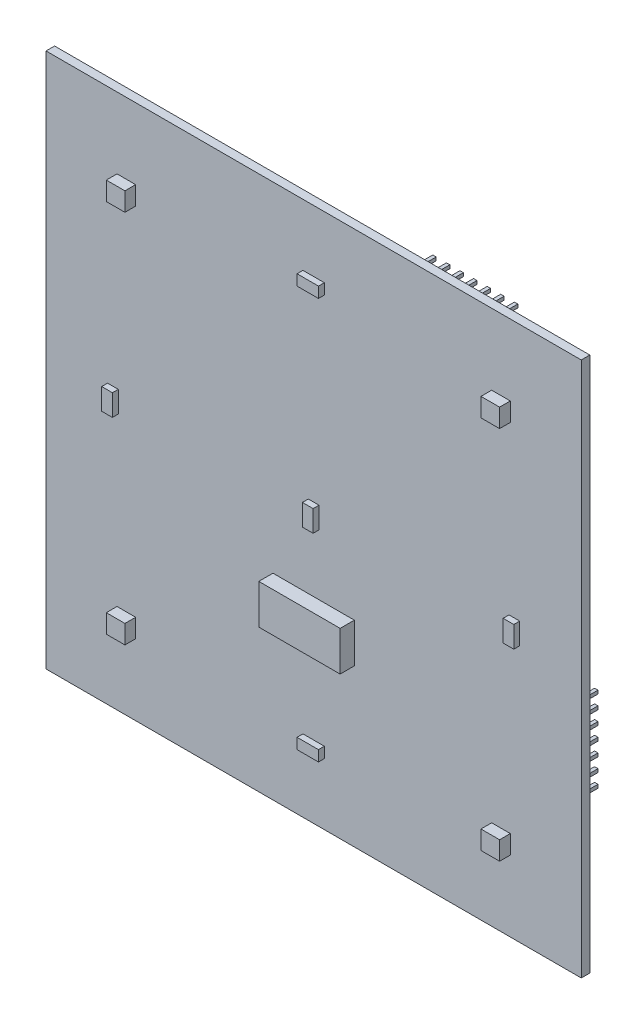
SolidWorks part; units mm, degrees
ref_plane "正面" through (0, 0, 0) normal (0, 0, 1) x (1, 0, 0)
ref_plane "平面" through (0, 0, 0) normal (0, 1, 0) x (1, 0, 0)
ref_plane "右側面" through (0, 0, 0) normal (1, 0, 0) x (0, 0, -1)
sketch "ｽｹｯﾁ1" plane through (0, 0, 0) normal (0, 0, 1) x (1, 0, 0)
  line L0 (-50, 0) -> (50, 0) construction
  line L1 (-50, 50) -> (50, 50)
  line L2 (-50, 50) -> (-50, -50)
  line L3 (-50, -50) -> (50, -50)
  line L4 (50, 50) -> (50, -50)
  line L5 (0, -50) -> (0, 50) construction
  point P8 (0, 0)
  dimension "D1" = 100
  dimension "D2" = 100
  dimension "D3" = 0
  dimension "D4" = 0
extrude "ﾎﾞｽ - 押し出し1" add sketch "ｽｹｯﾁ1" along normal blind 1.6
sketch "ｽｹｯﾁ4" plane through (0, 0, 0) normal (0, 0, -1) x (-1, 0, 0)
  line L0 (-50, -50) -> (-50, 50) construction
  line L1 (11.11, -41.35) -> (28.89, -41.35)
  line L2 (11.11, -41.35) -> (11.11, -43.85)
  line L3 (11.11, -43.85) -> (28.89, -43.85)
  line L4 (28.89, -41.35) -> (28.89, -43.85)
  line L5 (50, -50) -> (-50, -50) construction
  line L6 (50, 50) -> (50, -50) construction
  line L8 (-43.85, -11.11) -> (-41.35, -11.11)
  line L9 (-43.85, -11.11) -> (-43.85, -28.89)
  line L10 (-43.85, -28.89) -> (-41.35, -28.89)
  line L11 (-41.35, -11.11) -> (-41.35, -28.89)
  line L12 (-28.89, 43.85) -> (-11.11, 43.85)
  line L13 (-28.89, 43.85) -> (-28.89, 41.35)
  line L14 (-28.89, 41.35) -> (-11.11, 41.35)
  line L15 (-11.11, 43.85) -> (-11.11, 41.35)
  line L16 (-50, 50) -> (50, 50) construction
  line L18 (41.35, 28.89) -> (43.85, 28.89)
  line L19 (41.35, 28.89) -> (41.35, 11.11)
  line L20 (41.35, 11.11) -> (43.85, 11.11)
  line L21 (43.85, 28.89) -> (43.85, 11.11)
  point P4 (28.89, -42.6)
  point P7 (20, -43.85)
  point P14 (-43.85, -20)
  point P15 (-42.6, -28.89)
  point P22 (-28.89, 42.6)
  point P25 (43.85, 20)
  point P26 (-20, 43.85)
  point P31 (42.6, 28.89)
  dimension "D1" = 7.4
  dimension "D2" = 30
  dimension "D3" = 2.5
  dimension "D4" = 17.78
  dimension "D5" = 2.5
  dimension "D6" = 17.78
  dimension "D7" = 30
  dimension "D8" = 7.4
  dimension "D9" = 2.5
  dimension "D10" = 7.4
  dimension "D11" = 30
  dimension "D12" = 17.78
  dimension "D13" = 17.78
  dimension "D14" = 2.5
  dimension "D15" = 30
  dimension "D16" = 7.4
extrude "ﾎﾞｽ - 押し出し2" add sketch "ｽｹｯﾁ4" along normal blind 2.5
sketch "ｽｹｯﾁ5" plane through (0, 0, -2.5) normal (0, 0, -1) x (-1, 0, 0)
  line L1 (-20.32, 42.92) -> (-19.68, 42.92)
  line L2 (-20.32, 42.92) -> (-20.32, 42.28)
  line L3 (-20.32, 42.28) -> (-19.68, 42.28)
  line L4 (-19.68, 42.92) -> (-19.68, 42.28)
  line L5 (43.85, 28.89) -> (41.35, 28.89) construction
  line L6 (-11.11, 43.85) -> (-28.89, 43.85) construction
  line L7 (-28.89, 43.85) -> (-28.89, 41.35) construction
  line L8 (-43.85, -28.89) -> (-41.35, -28.89) construction
  line L9 (-17.78, 42.92) -> (-17.14, 42.92)
  line L10 (-17.78, 42.92) -> (-17.78, 42.28)
  line L11 (-17.78, 42.28) -> (-17.14, 42.28)
  line L12 (-17.14, 42.92) -> (-17.14, 42.28)
  line L13 (-15.24, 42.92) -> (-14.6, 42.92)
  line L14 (-15.24, 42.92) -> (-15.24, 42.28)
  line L15 (-15.24, 42.28) -> (-14.6, 42.28)
  line L16 (-14.6, 42.92) -> (-14.6, 42.28)
  line L17 (-12.7, 42.92) -> (-12.06, 42.92)
  line L18 (-12.7, 42.92) -> (-12.7, 42.28)
  line L19 (-12.7, 42.28) -> (-12.06, 42.28)
  line L20 (-12.06, 42.92) -> (-12.06, 42.28)
  line L21 (-22.86, 42.92) -> (-22.22, 42.92)
  line L22 (-22.86, 42.92) -> (-22.86, 42.28)
  line L23 (-22.86, 42.28) -> (-22.22, 42.28)
  line L24 (-22.22, 42.92) -> (-22.22, 42.28)
  line L25 (-25.4, 42.92) -> (-24.76, 42.92)
  line L26 (-25.4, 42.92) -> (-25.4, 42.28)
  line L27 (-25.4, 42.28) -> (-24.76, 42.28)
  line L28 (-24.76, 42.92) -> (-24.76, 42.28)
  line L29 (-27.94, 42.92) -> (-27.3, 42.92)
  line L30 (-27.94, 42.92) -> (-27.94, 42.28)
  line L31 (-27.94, 42.28) -> (-27.3, 42.28)
  line L32 (-27.3, 42.92) -> (-27.3, 42.28)
  line L33 (-42.92, -19.68) -> (-42.28, -19.68)
  line L34 (-42.92, -19.68) -> (-42.92, -20.32)
  line L35 (-42.92, -20.32) -> (-42.28, -20.32)
  line L36 (-42.28, -19.68) -> (-42.28, -20.32)
  line L37 (-43.85, -11.11) -> (-43.85, -28.89) construction
  line L38 (43.85, 11.11) -> (43.85, 28.89) construction
  line L39 (-42.92, -22.22) -> (-42.28, -22.22)
  line L40 (-42.92, -22.22) -> (-42.92, -22.86)
  line L41 (-42.92, -22.86) -> (-42.28, -22.86)
  line L42 (-42.28, -22.22) -> (-42.28, -22.86)
  line L44 (42.28, 19.68) -> (42.92, 19.68)
  line L45 (-42.92, -24.76) -> (-42.28, -24.76)
  line L46 (-42.92, -24.76) -> (-42.92, -25.4)
  line L47 (-42.92, -25.4) -> (-42.28, -25.4)
  line L48 (-42.28, -24.76) -> (-42.28, -25.4)
  line L49 (-42.92, -27.3) -> (-42.28, -27.3)
  line L50 (-42.92, -27.3) -> (-42.92, -27.94)
  line L51 (-42.92, -27.94) -> (-42.28, -27.94)
  line L52 (-42.28, -27.3) -> (-42.28, -27.94)
  line L53 (-42.92, -17.14) -> (-42.28, -17.14)
  line L54 (-42.92, -17.14) -> (-42.92, -17.78)
  line L55 (-42.92, -17.78) -> (-42.28, -17.78)
  line L56 (-42.28, -17.14) -> (-42.28, -17.78)
  line L57 (-42.92, -14.6) -> (-42.28, -14.6)
  line L58 (-42.92, -14.6) -> (-42.92, -15.24)
  line L59 (-42.92, -15.24) -> (-42.28, -15.24)
  line L60 (-42.28, -14.6) -> (-42.28, -15.24)
  line L61 (-42.92, -12.06) -> (-42.28, -12.06)
  line L62 (-42.92, -12.06) -> (-42.92, -12.7)
  line L63 (-42.92, -12.7) -> (-42.28, -12.7)
  line L64 (-42.28, -12.06) -> (-42.28, -12.7)
  line L69 (42.28, 19.68) -> (42.28, 20.32)
  line L70 (11.11, -43.85) -> (28.89, -43.85) construction
  line L71 (42.28, 17.78) -> (42.92, 17.78)
  line L72 (42.28, 20.32) -> (42.92, 20.32)
  line L73 (42.92, 19.68) -> (42.92, 20.32)
  line L75 (42.28, 17.78) -> (42.28, 17.14)
  line L76 (42.28, 17.14) -> (42.92, 17.14)
  line L77 (42.92, 17.78) -> (42.92, 17.14)
  line L78 (42.28, 15.24) -> (42.92, 15.24)
  line L79 (42.28, 15.24) -> (42.28, 14.6)
  line L80 (42.28, 14.6) -> (42.92, 14.6)
  line L81 (42.92, 15.24) -> (42.92, 14.6)
  line L82 (42.28, 12.7) -> (42.92, 12.7)
  line L83 (42.28, 12.7) -> (42.28, 12.06)
  line L84 (42.28, 12.06) -> (42.92, 12.06)
  line L85 (42.92, 12.7) -> (42.92, 12.06)
  line L86 (42.28, 22.86) -> (42.92, 22.86)
  line L87 (42.28, 22.86) -> (42.28, 22.22)
  line L88 (42.28, 22.22) -> (42.92, 22.22)
  line L89 (42.92, 22.86) -> (42.92, 22.22)
  line L90 (42.28, 25.4) -> (42.92, 25.4)
  line L91 (42.28, 25.4) -> (42.28, 24.76)
  line L92 (42.28, 24.76) -> (42.92, 24.76)
  line L93 (42.92, 25.4) -> (42.92, 24.76)
  line L94 (42.28, 27.94) -> (42.92, 27.94)
  line L95 (42.28, 27.94) -> (42.28, 27.3)
  line L96 (42.28, 27.3) -> (42.92, 27.3)
  line L97 (42.92, 27.94) -> (42.92, 27.3)
  line L98 (19.68, -42.28) -> (20.32, -42.28)
  line L99 (19.68, -42.28) -> (19.68, -42.92)
  line L100 (19.68, -42.92) -> (20.32, -42.92)
  line L101 (20.32, -42.28) -> (20.32, -42.92)
  line L102 (11.11, -41.35) -> (11.11, -43.85) construction
  line L104 (17.14, -42.28) -> (17.78, -42.28)
  line L105 (17.14, -42.28) -> (17.14, -42.92)
  line L106 (17.14, -42.92) -> (17.78, -42.92)
  line L107 (17.78, -42.28) -> (17.78, -42.92)
  line L108 (14.6, -42.28) -> (15.24, -42.28)
  line L109 (14.6, -42.28) -> (14.6, -42.92)
  line L110 (14.6, -42.92) -> (15.24, -42.92)
  line L111 (15.24, -42.28) -> (15.24, -42.92)
  line L112 (12.06, -42.28) -> (12.7, -42.28)
  line L113 (12.06, -42.28) -> (12.06, -42.92)
  line L114 (12.06, -42.92) -> (12.7, -42.92)
  line L115 (12.7, -42.28) -> (12.7, -42.92)
  line L116 (22.22, -42.28) -> (22.86, -42.28)
  line L117 (22.22, -42.28) -> (22.22, -42.92)
  line L118 (22.22, -42.92) -> (22.86, -42.92)
  line L119 (22.86, -42.28) -> (22.86, -42.92)
  line L120 (24.76, -42.28) -> (25.4, -42.28)
  line L121 (24.76, -42.28) -> (24.76, -42.92)
  line L122 (24.76, -42.92) -> (25.4, -42.92)
  line L123 (25.4, -42.28) -> (25.4, -42.92)
  line L124 (27.3, -42.28) -> (27.94, -42.28)
  line L125 (27.3, -42.28) -> (27.3, -42.92)
  line L126 (27.3, -42.92) -> (27.94, -42.92)
  line L127 (27.94, -42.28) -> (27.94, -42.92)
  point P4 (-20, 42.92)
  point P7 (-20, 43.85)
  point P8 (-20.32, 42.6)
  point P11 (-28.89, 42.6)
  point P16 (-20, 42.28)
  point P17 (-17.46, 42.28)
  point P22 (-14.92, 42.28)
  point P27 (-12.38, 42.28)
  point P40 (-22.54, 42.28)
  point P41 (-25.08, 42.28)
  point P42 (-27.62, 42.28)
  point P47 (-42.6, -20.32)
  point P50 (-42.6, -28.89)
  point P53 (-42.92, -20)
  point P54 (-43.85, -20)
  point P59 (-42.28, -22.54)
  point P60 (-42.28, -20)
  point P61 (-42.28, -25.08)
  point P70 (-42.28, -27.62)
  point P83 (-42.28, -17.46)
  point P84 (-42.28, -14.92)
  point P85 (-42.28, -12.38)
  point P90 (42.6, 19.68)
  point P93 (42.6, 28.89)
  point P94 (42.92, 20)
  point P97 (43.85, 20)
  point P110 (42.28, 12.38)
  point P111 (42.28, 14.92)
  point P112 (42.28, 17.46)
  point P113 (42.28, 20)
  point P126 (42.28, 22.54)
  point P127 (42.28, 25.08)
  point P128 (42.28, 27.62)
  point P133 (20, -42.92)
  point P136 (20, -43.85)
  point P139 (11.11, -42.6)
  point P140 (19.68, -42.6)
  point P165 (17.46, -42.28)
  point P166 (20, -42.28)
  point P167 (14.92, -42.28)
  point P168 (12.38, -42.28)
  point P169 (22.54, -42.28)
  point P170 (25.08, -42.28)
  point P171 (27.62, -42.28)
  point P173 (12.06, -42.6)
  point P174 (14.6, -42.6)
  point P175 (17.14, -42.6)
  point P176 (22.22, -42.6)
  point P177 (24.76, -42.6)
  point P178 (27.3, -42.6)
  point P179 (-42.6, -27.3)
  point P180 (-42.6, -24.76)
  point P181 (-42.6, -22.22)
  point P182 (-42.6, -19.68)
  point P183 (-42.6, -17.14)
  point P184 (-42.6, -14.6)
  point P185 (-42.6, -12.06)
  point P186 (-27.94, 42.6)
  point P187 (-25.4, 42.6)
  point P188 (-22.86, 42.6)
  point P189 (-17.78, 42.6)
  point P190 (-15.24, 42.6)
  point P191 (-12.7, 42.6)
  point P192 (42.6, 15.24)
  point P193 (42.6, 17.78)
  point P194 (42.6, 20.32)
  point P195 (42.6, 22.86)
  point P196 (42.6, 25.4)
  point P197 (42.6, 27.94)
  point P198 (42.6, 12.7)
  dimension "D1" = 0.64
  dimension "D2" = 0.64
  dimension "D3" = 0.64
  dimension "D4" = 0.64
  dimension "D5" = 2.54
  dimension "D6" = 0.64
  dimension "D7" = 2.54
  dimension "D8" = 0.64
  dimension "D9" = 0.64
  dimension "D10" = 0.64
  dimension "D11" = 2.54
  dimension "D12" = 0.64
  dimension "D13" = 0.64
  dimension "D14" = 0.64
  dimension "D15" = 2.54
  dimension "D16" = 0.64
  dimension "D17" = 0.64
  dimension "D18" = 0.64
  dimension "D19" = 2.54
  dimension "D20" = 2.54
  dimension "D21" = 0.64
  dimension "D22" = 0.64
  dimension "D23" = 0.64
  dimension "D24" = 0.64
  dimension "D25" = 2.54
  dimension "D26" = 0.64
  dimension "D27" = 2.54
  dimension "D28" = 0.64
  dimension "D29" = 2.54
  dimension "D30" = 0.64
  dimension "D31" = 0.64
  dimension "D32" = 0.64
  dimension "D33" = 0.64
  dimension "D34" = 2.54
  dimension "D35" = 2.54
  dimension "D36" = 0.64
  dimension "D37" = 0.64
  dimension "D38" = 0.64
  dimension "D39" = 2.54
  dimension "D40" = 0.64
  dimension "D41" = 0.64
  dimension "D42" = 0.64
  dimension "D43" = 0.64
  dimension "D44" = 0.64
  dimension "D45" = 0.64
  dimension "D46" = 2.54
  dimension "D47" = 2.54
  dimension "D48" = 2.54
  dimension "D49" = 2.54
  dimension "D50" = 0.64
  dimension "D51" = 0.64
  dimension "D52" = 0.64
  dimension "D53" = 0.64
  dimension "D54" = 2.54
  dimension "D55" = 0.64
  dimension "D56" = 0.64
  dimension "D57" = 2.54
  dimension "D58" = 0.64
  dimension "D59" = 0.64
  dimension "D60" = 0.64
  dimension "D61" = 0.64
  dimension "D62" = 0.64
  dimension "D63" = 2.54
  dimension "D64" = 2.54
  dimension "D65" = 2.54
  dimension "D66" = 0.64
  dimension "D67" = 0.64
  dimension "D68" = 0.64
  dimension "D69" = 0.64
  dimension "D70" = 0.64
  dimension "D71" = 0.64
  dimension "D72" = 2.54
  dimension "D73" = 2.54
  dimension "D74" = 2.54
  dimension "D75" = 0.64
  dimension "D76" = 0.64
  dimension "D77" = 0.64
  dimension "D78" = 0.64
  dimension "D79" = 0.64
  dimension "D80" = 0.64
extrude "ﾎﾞｽ - 押し出し3" add sketch "ｽｹｯﾁ5" along normal blind 6.1
sketch "ｽｹｯﾁ6" plane through (0, 0, 1.6) normal (0, 0, 1) x (1, 0, 0)
  line L0 (-50, -50) -> (50, -50) construction
  line L1 (-36.74, -33.26) -> (-33.26, -33.26)
  line L2 (-36.74, -33.26) -> (-36.74, -36.74)
  line L3 (-36.74, -36.74) -> (-33.26, -36.74)
  line L4 (-33.26, -33.26) -> (-33.26, -36.74)
  line L5 (-50, 50) -> (-50, -50) construction
  line L6 (50, 50) -> (-50, 50) construction
  line L7 (-36.74, 36.74) -> (-33.26, 36.74)
  line L8 (-36.74, 36.74) -> (-36.74, 33.26)
  line L9 (-36.74, 33.26) -> (-33.26, 33.26)
  line L10 (-33.26, 36.74) -> (-33.26, 33.26)
  line L11 (50, -50) -> (50, 50) construction
  line L12 (33.26, -33.26) -> (36.74, -33.26)
  line L13 (33.26, -33.26) -> (33.26, -36.74)
  line L14 (33.26, -36.74) -> (36.74, -36.74)
  line L15 (36.74, -33.26) -> (36.74, -36.74)
  line L17 (33.26, 36.74) -> (36.74, 36.74)
  line L18 (33.26, 36.74) -> (33.26, 33.26)
  line L19 (33.26, 33.26) -> (36.74, 33.26)
  line L20 (36.74, 36.74) -> (36.74, 33.26)
  point P4 (-36.74, -35)
  point P7 (-35, -36.74)
  point P14 (-36.74, 35)
  point P17 (-35, 36.74)
  point P22 (35, -36.74)
  point P25 (36.74, -35)
  point P30 (35, 36.74)
  point P31 (36.74, 35)
  dimension "D1" = 3.48
  dimension "D2" = 3.48
  dimension "D3" = 15
  dimension "D4" = 15
  dimension "D5" = 3.48
  dimension "D6" = 3.48
  dimension "D7" = 15
  dimension "D8" = 15
  dimension "D9" = 15
  dimension "D10" = 15
  dimension "D11" = 3.48
  dimension "D12" = 3.48
  dimension "D13" = 15
  dimension "D14" = 15
  dimension "D15" = 3.48
  dimension "D16" = 3.48
extrude "ﾎﾞｽ - 押し出し4" add sketch "ｽｹｯﾁ6" along normal blind 2
sketch "ｽｹｯﾁ7" plane through (0, 0, 1.6) normal (0, 0, 1) x (1, 0, 0)
  line L0 (-50, -50) -> (50, -50) construction
  line L1 (-38.5, 2) -> (-36.5, 2)
  line L2 (-38.5, 2) -> (-38.5, -2)
  line L3 (-38.5, -2) -> (-36.5, -2)
  line L4 (-36.5, 2) -> (-36.5, -2)
  line L5 (-50, 50) -> (-50, -50) construction
  line L6 (50, -50) -> (50, 50) construction
  line L7 (36.5, 2) -> (38.5, 2)
  line L8 (36.5, 2) -> (36.5, -2)
  line L9 (36.5, -2) -> (38.5, -2)
  line L10 (38.5, 2) -> (38.5, -2)
  line L11 (50, 50) -> (-50, 50) construction
  line L12 (-2, 38.5) -> (2, 38.5)
  line L13 (-2, 38.5) -> (-2, 36.5)
  line L14 (-2, 36.5) -> (2, 36.5)
  line L15 (2, 38.5) -> (2, 36.5)
  line L17 (-2, -36.5) -> (2, -36.5)
  line L18 (-2, -36.5) -> (-2, -38.5)
  line L19 (-2, -38.5) -> (2, -38.5)
  line L20 (2, -36.5) -> (2, -38.5)
  line L21 (-1, 2) -> (1, 2)
  line L22 (-1, 2) -> (-1, -2)
  line L23 (-1, -2) -> (1, -2)
  line L24 (1, 2) -> (1, -2)
  point P4 (-38.5, 0)
  point P7 (-37.5, -2)
  point P14 (37.5, 2)
  point P17 (38.5, 0)
  point P22 (-2, 37.5)
  point P25 (0, 38.5)
  point P30 (-2, -37.5)
  point P31 (0, -38.5)
  point P36 (1, 0)
  point P37 (36.5, 0)
  point P38 (0, 36.5)
  point P39 (0, 2)
  dimension "D1" = 4
  dimension "D2" = 2
  dimension "D3" = 50
  dimension "D4" = 12.5
  dimension "D5" = 4
  dimension "D6" = 2
  dimension "D7" = 12.5
  dimension "D8" = 50
  dimension "D9" = 4
  dimension "D10" = 2
  dimension "D11" = 12.5
  dimension "D12" = 50
  dimension "D13" = 4
  dimension "D14" = 2
  dimension "D15" = 12.5
  dimension "D16" = 50
  dimension "D17" = 4
  dimension "D18" = 2
extrude "ﾎﾞｽ - 押し出し5" add sketch "ｽｹｯﾁ7" along normal blind 1.1
sketch "ｽｹｯﾁ8" plane through (0, 0, 1.6) normal (0, 0, 1) x (1, 0, 0)
  line L0 (-50, -50) -> (50, -50) construction
  line L1 (-7.6, -13.3) -> (7.6, -13.3)
  line L2 (-7.6, -13.3) -> (-7.6, -20.7)
  line L3 (-7.6, -20.7) -> (7.6, -20.7)
  line L4 (7.6, -13.3) -> (7.6, -20.7)
  point P4 (-7.6, -17)
  point P7 (0, -50)
  point P8 (0, -20.7)
  dimension "D1" = 7.4
  dimension "D2" = 15.2
  dimension "D3" = 33
extrude "ﾎﾞｽ - 押し出し6" add sketch "ｽｹｯﾁ8" along normal blind 2.65
sketch "ｽｹｯﾁ9" plane through (0, 0, 0) normal (0, 0, -1) x (-1, 0, 0)
  line L1 (-4.61, 19.83) -> (3.01, 19.83)
  line L2 (-4.61, 19.83) -> (-4.61, 17.33)
  line L3 (-4.61, 17.33) -> (3.01, 17.33)
  line L4 (3.01, 19.83) -> (3.01, 17.33)
  line L5 (50, 50) -> (50, -50) construction
  line L6 (50, -50) -> (-50, -50) construction
  point P4 (-0.8, 19.83)
  point P7 (3.01, 18.58)
  dimension "D1" = 7.62
  dimension "D2" = 2.5
  dimension "D3" = 50.8
  dimension "D4" = 68.58
extrude "ﾎﾞｽ - 押し出し7" add sketch "ｽｹｯﾁ9" along normal blind 2.5
sketch "ｽｹｯﾁ11" plane through (0, 0, -2.5) normal (0, 0, -1) x (-1, 0, 0)
  line L0 (3.01, 19.83) -> (-4.61, 19.83) construction
  line L1 (-1.12, 18.9) -> (-0.48, 18.9)
  line L2 (-1.12, 18.9) -> (-1.12, 18.26)
  line L3 (-1.12, 18.26) -> (-0.48, 18.26)
  line L4 (-0.48, 18.9) -> (-0.48, 18.26)
  line L5 (-4.61, 19.83) -> (-4.61, 17.33) construction
  line L7 (-3.66, 18.9) -> (-3.02, 18.9)
  line L8 (-3.66, 18.9) -> (-3.66, 18.26)
  line L9 (-3.66, 18.26) -> (-3.02, 18.26)
  line L10 (-3.02, 18.9) -> (-3.02, 18.26)
  line L11 (1.42, 18.9) -> (2.06, 18.9)
  line L12 (1.42, 18.9) -> (1.42, 18.26)
  line L13 (1.42, 18.26) -> (2.06, 18.26)
  line L14 (2.06, 18.9) -> (2.06, 18.26)
  point P4 (-0.8, 18.9)
  point P7 (-0.8, 19.83)
  point P8 (-1.12, 18.58)
  point P11 (-4.61, 18.58)
  point P20 (-3.34, 18.26)
  point P21 (-0.8, 18.26)
  point P22 (1.74, 18.26)
  point P23 (-3.66, 18.58)
  point P25 (1.42, 18.58)
  dimension "D1" = 0.64
  dimension "D2" = 0.64
  dimension "D3" = 0.64
  dimension "D4" = 0.64
  dimension "D5" = 0.64
  dimension "D6" = 2.54
  dimension "D7" = 2.54
extrude "ﾎﾞｽ - 押し出し8" add sketch "ｽｹｯﾁ11" along normal blind 6.1
sketch "ｽｹｯﾁ15" plane through (0, 0, 0) normal (0, 0, -1) x (-1, 0, 0)
  line L0 (0, 0) -> (0, -50) construction
  line L1 (-5.08, -29.75) -> (5.08, -29.75)
  line L2 (-5.08, -29.75) -> (-5.08, -32.25)
  line L3 (-5.08, -32.25) -> (5.08, -32.25)
  line L4 (5.08, -29.75) -> (5.08, -32.25)
  line L5 (50, -50) -> (-50, -50) construction
  point P9 (0, -29.75)
  point P10 (-5.08, -31)
  dimension "D1" = 10.16
  dimension "D2" = 2.5
  dimension "D3" = 19
extrude "ﾎﾞｽ - 押し出し11" add sketch "ｽｹｯﾁ15" along normal blind 2.5
sketch "ｽｹｯﾁ16" plane through (0, 0, -2.5) normal (0, 0, -1) x (-1, 0, 0)
  line L0 (-5.08, -31) -> (5.08, -31) construction
  line L1 (-4.13, -30.68) -> (-3.49, -30.68)
  line L2 (-4.13, -30.68) -> (-4.13, -31.32)
  line L3 (-4.13, -31.32) -> (-3.49, -31.32)
  line L4 (-3.49, -30.68) -> (-3.49, -31.32)
  line L5 (-0.95, -30.68) -> (-1.59, -30.68)
  line L6 (-0.95, -30.68) -> (-0.95, -31.32)
  line L7 (-0.95, -31.32) -> (-1.59, -31.32)
  line L8 (-1.59, -30.68) -> (-1.59, -31.32)
  line L9 (0.95, -30.68) -> (1.59, -30.68)
  line L10 (0.95, -30.68) -> (0.95, -31.32)
  line L11 (0.95, -31.32) -> (1.59, -31.32)
  line L12 (1.59, -30.68) -> (1.59, -31.32)
  line L13 (3.49, -30.68) -> (4.13, -30.68)
  line L14 (3.49, -30.68) -> (3.49, -31.32)
  line L15 (3.49, -31.32) -> (4.13, -31.32)
  line L16 (4.13, -30.68) -> (4.13, -31.32)
  line L17 (-5.08, -29.75) -> (-5.08, -32.25) construction
  line L18 (5.08, -32.25) -> (5.08, -29.75) construction
  line L19 (-5.08, -29.75) -> (-5.08, -32.25) construction
  line L20 (5.08, -32.25) -> (5.08, -29.75) construction
  point P22 (-4.13, -31)
  point P23 (-0.95, -31)
  point P24 (0.95, -31)
  point P25 (3.49, -31)
  point P26 (-3.81, -31.32)
  point P27 (-1.27, -31.32)
  point P28 (1.27, -31.32)
  point P29 (3.81, -31.32)
  point P30 (1.6593, -31.4718)
  dimension "D1" = 0.64
  dimension "D2" = 0.64
  dimension "D3" = 2.54
  dimension "D4" = 0.64
  dimension "D5" = 0.64
  dimension "D6" = 0.64
  dimension "D7" = 2.54
  dimension "D8" = 2.54
  dimension "D9" = 1.27
  dimension "D10" = 1.27
extrude "ﾎﾞｽ - 押し出し12" add sketch "ｽｹｯﾁ16" along normal blind 6.1
sketch "ｽｹｯﾁ13" plane through (0, 0, 0) normal (0, 0, -1) x (-1, 0, 0)
  line L0 (-50, -50) -> (-50, 50) construction
  line L7 (-50, 50) -> (50, 50) construction
  line L8 (50, -50) -> (-50, -50) construction
  line L15 (50, 50) -> (50, -50) construction
  line L23 (32, -30) -> (31, -28.2679)
  line L24 (31, -28.2679) -> (29, -28.2679)
  line L25 (29, -28.2679) -> (28, -30)
  line L26 (28, -30) -> (29, -31.7321)
  line L27 (29, -31.7321) -> (31, -31.7321)
  line L28 (31, -31.7321) -> (32, -30)
  line L29 (-28, -30) -> (-29, -28.2679)
  line L30 (-29, -28.2679) -> (-31, -28.2679)
  line L31 (-31, -28.2679) -> (-32, -30)
  line L32 (-32, -30) -> (-31, -31.7321)
  line L33 (-31, -31.7321) -> (-29, -31.7321)
  line L34 (-29, -31.7321) -> (-28, -30)
  line L35 (32, 30) -> (31, 31.7321)
  line L36 (31, 31.7321) -> (29, 31.7321)
  line L37 (29, 31.7321) -> (28, 30)
  line L38 (28, 30) -> (29, 28.2679)
  line L39 (29, 28.2679) -> (31, 28.2679)
  line L40 (31, 28.2679) -> (32, 30)
  line L41 (-28, 30) -> (-29, 31.7321)
  line L42 (-29, 31.7321) -> (-31, 31.7321)
  line L43 (-31, 31.7321) -> (-32, 30)
  line L44 (-32, 30) -> (-31, 28.2679)
  line L45 (-31, 28.2679) -> (-29, 28.2679)
  line L46 (-29, 28.2679) -> (-28, 30)
  circle A0 centre (-30, 30) radius 2 construction
  circle A1 centre (-30, -30) radius 2 construction
  circle A2 centre (30, 30) radius 2 construction
  circle A3 centre (30, -30) radius 2 construction
  dimension "D1" = 20
  dimension "D2" = 20
  dimension "D3" = 20
  dimension "D4" = 20
  dimension "D5" = 20
  dimension "D6" = 20
  dimension "D7" = 20
  dimension "D8" = 20
extrude "ﾎﾞｽ - 押し出し9" add sketch "ｽｹｯﾁ13" along normal blind 6
sketch "ｽｹｯﾁ14" plane through (0, 0, -6) normal (0, 0, -1) x (-1, 0, 0)
  line L2 (0, -39) -> (0, -41)
  line L3 (0, -41) -> (39, -41)
  line L4 (39, -41) -> (39, 0)
  line L5 (39, 0) -> (41, 0)
  line L6 (41, 0) -> (41, 39)
  line L7 (41, 39) -> (0, 39)
  line L8 (0, 39) -> (0, 41)
  line L9 (0, 41) -> (-39, 41)
  line L11 (-39, 41) -> (-39, 0)
  line L12 (-39, 0) -> (-41, 0)
  line L13 (-41, 0) -> (-41, -39)
  line L14 (-41, -39) -> (0, -39)
  line L21 (-29, 31.7321) -> (-31, 31.7321) construction
  line L22 (-4.61, 19.83) -> (3.01, 19.83)
  line L23 (-4.61, 19.83) -> (-4.61, 17.33)
  line L24 (-4.61, 17.33) -> (3.01, 17.33)
  line L25 (3.01, 19.83) -> (3.01, 17.33)
  line L26 (31, 31.7321) -> (29, 31.7321) construction
  line L27 (31, -28.2679) -> (29, -28.2679) construction
  line L28 (-29, -28.2679) -> (-31, -28.2679) construction
  line L29 (-5.08, -29.75) -> (5.08, -29.75)
  line L30 (-5.08, -29.75) -> (-5.08, -32.25)
  line L31 (-5.08, -32.25) -> (5.08, -32.25)
  line L32 (5.08, -29.75) -> (5.08, -32.25)
  circle A0 centre (-30, 30) radius 1
  circle A1 centre (30, 30) radius 1
  circle A2 centre (30, -30) radius 1
  circle A3 centre (-30, -30) radius 1
  point P28 (-30, 31.7321)
  point P37 (30, 31.7321)
  point P41 (30, -28.2679)
  point P47 (-30, -28.2679)
  dimension "D11" = 10.16
  dimension "D1" = 39
  dimension "D2" = 41
  dimension "D3" = 41
  dimension "D4" = 39
  dimension "D5" = 41
  dimension "D6" = 39
  dimension "D7" = 41
  dimension "D8" = 39
  dimension "D9" = 2.5
  dimension "D10" = 7.62
  dimension "D12" = 2.5
extrude "ﾎﾞｽ - 押し出し10" add sketch "ｽｹｯﾁ14" along normal blind 2 separate body
